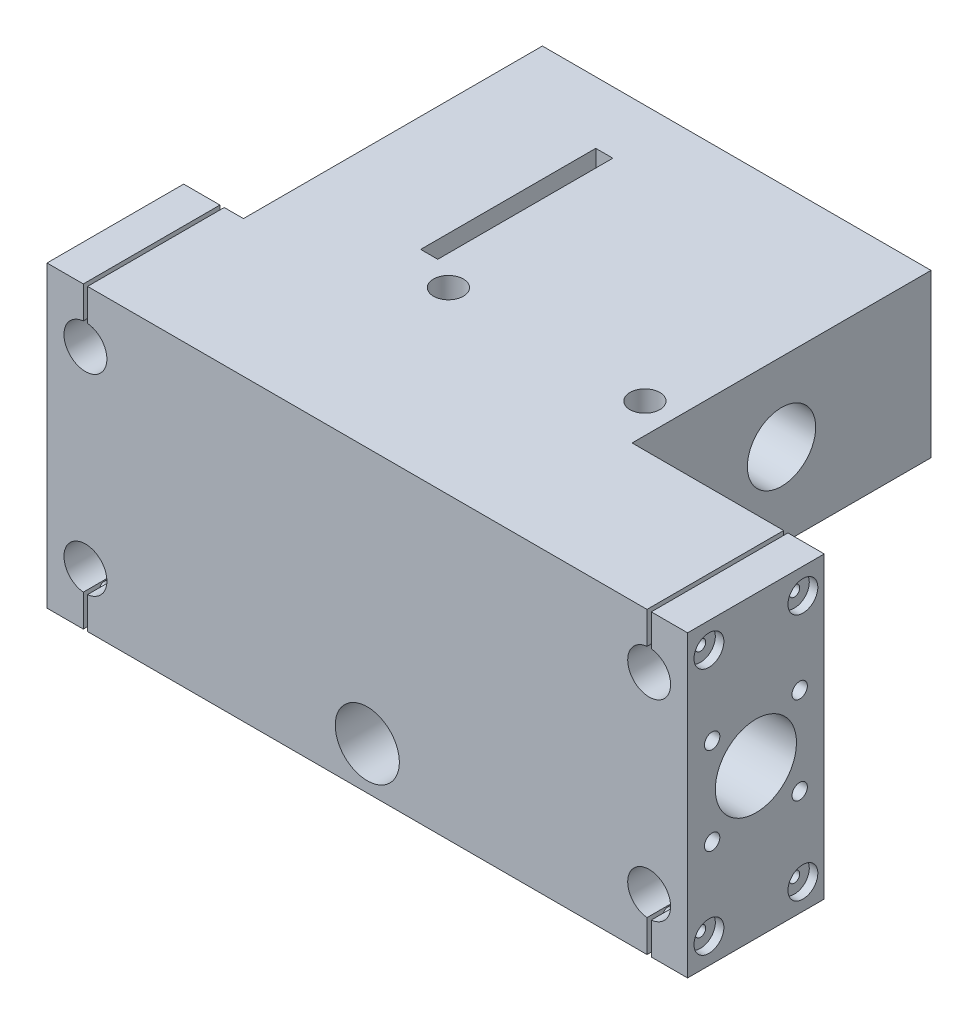
SolidWorks part; units mm, degrees
material "1060 Alloy"
ref_plane "Front Plane" through (0, 0, 0) normal (0, 0, 1) x (1, 0, 0)
ref_plane "Top Plane" through (0, 0, 0) normal (0, 1, 0) x (1, 0, 0)
ref_plane "Right Plane" through (0, 0, 0) normal (1, 0, 0) x (0, 0, -1)
sketch "Sketch1" plane through (0, 0, 0) normal (0, 0, 1) x (1, 0, 0)
  line L1 (-150, 0) -> (0, 0)
  line L2 (-150, 0) -> (-150, -70)
  line L3 (-150, -70) -> (0, -70)
  line L4 (0, 0) -> (0, -70)
  dimension "D1" = 150
  dimension "D2" = 70
extrude "Boss-Extrude1" add sketch "Sketch1" along normal blind 32
sketch "Sketch2" plane through (-150, 0, 0) normal (-1, 0, 0) x (0, 0, 1)
  line L0 (16, 0) -> (16, -70) construction
  line L1 (32, 0) -> (0, 0) construction
  line L2 (32, -70) -> (0, -70) construction
  line L3 (0, -35) -> (32, -35) construction
  line L4 (0, 0) -> (0, -70) construction
  line L5 (32, 0) -> (32, -70) construction
  circle A0 centre (16, -35) radius 9.5
  dimension "D1" = 19
extrude "Linear_bearing-cut-1" cut sketch "Sketch2" against normal blind 55
sketch "Sketch5" plane through (0, 0, 32) normal (0, 0, 1) x (1, 0, 0)
  line L0 (-75, 0) -> (-75, -70) construction
  line L1 (0, 0) -> (-150, 0) construction
  line L2 (-150, -70) -> (0, -70) construction
  line L3 (0, -35) -> (-150, -35) construction
  line L4 (0, -70) -> (0, 0) construction
  line L5 (-150, 0) -> (-150, -70) construction
  line L6 (-141, 0) -> (-141, -12.5) construction
  line L7 (-141, -12.5) -> (-9, -12.5) construction
  line L8 (-9, -12.5) -> (-9, 0) construction
  line L9 (-9, -57.5) -> (-9, -70) construction
  line L10 (-141, -57.5) -> (-9, -57.5) construction
  line L11 (-141, -70) -> (-141, -57.5) construction
  line L12 (-141.5, 0) -> (-141.5, -7.5)
  line L13 (-140.5, 0) -> (-140.5, -7.5)
  line L14 (-8.5, 0) -> (-8.5, -7.5)
  line L15 (-9.5, 0) -> (-9.5, -7.5)
  line L16 (-141.5, -70) -> (-141.5, -62.5)
  line L17 (-140.5, -70) -> (-140.5, -62.5)
  line L18 (-9.5, -70) -> (-9.5, -62.5)
  line L19 (-8.5, -70) -> (-8.5, -62.5)
  line L20 (-141.5, 0) -> (-140.5, 0)
  line L21 (-9.5, 0) -> (-8.5, 0)
  line L22 (-9.5, -70) -> (-8.5, -70)
  line L23 (-141.5, -70) -> (-140.5, -70)
  arc A0 (-141.5, -7.5) -> (-140.5, -7.5) centre (-141, -12.5) ccw
  arc A1 (-8.5, -7.5) -> (-9.5, -7.5) centre (-9, -12.5) cw
  arc A2 (-141.5, -62.5) -> (-140.5, -62.5) centre (-141, -57.5) cw
  arc A3 (-8.5, -62.5) -> (-9.5, -62.5) centre (-9, -57.5) ccw
  dimension "D1" = 9
  dimension "D3" = 12.5
  dimension "D5" = 0.5
  dimension "D6" = 7.5
extrude "Y-axis-shafts-cut" cut sketch "Sketch5" against normal through all
sketch "Sketch6" plane through (-95, 0, 0) normal (-1, 0, 0) x (0, 0, 1)
  line L0 (16, -25.5) -> (16, -44.5) construction
  circle A0 centre (16, -35) radius 9.5 construction
  circle A1 centre (16, -35) radius 9.5 construction
  circle A2 centre (16, -35) radius 6
  dimension "D1" = 12
sketch "Sketch7" plane through (0, 0, 0) normal (1, 0, 0) x (0, 0, -1)
  circle A0 centre (-16, -35) radius 9.5
  dimension "D1" = 19
extrude "Linear-bearing-cut-2" cut sketch "Sketch7" against normal blind 55
extrude "between-bearings" cut sketch "Sketch6" against normal through all
sketch "Sketch8" plane through (-150, 0, 0) normal (-1, 0, 0) x (0, 0, 1)
  line L0 (5, 0) -> (5, -6) construction
  line L1 (32, 0) -> (0, 0) construction
  line L2 (5, -6) -> (27, -6) construction
  line L3 (27, -6) -> (27, 0) construction
  line L4 (0, 0) -> (0, -70) construction
  line L5 (32, 0) -> (32, -70) construction
  line L6 (16, 0) -> (16, -70) construction
  line L7 (32, -70) -> (0, -70) construction
  line L8 (0, -35) -> (32, -35) construction
  line L9 (5, -39.9148) -> (4.7174, -39.9148) construction
  circle A0 centre (5, -6) radius 3.5
  circle A1 centre (27, -6) radius 3.5
  circle A2 centre (27, -64) radius 3.5
  circle A3 centre (5, -64) radius 3.5
  dimension "D4" = 7
  dimension "D1" = 5
  dimension "D3" = 6
extrude "shaft-holder-screw-cut" cut sketch "Sketch8" against normal blind 4
sketch "Sketch9" plane through (-146, 0, 0) normal (-1, 0, 0) x (0, 0, 1)
  line L0 (5, -2.5) -> (5, -9.5) construction
  line L1 (27, -2.5) -> (27, -9.5) construction
  line L2 (27, -60.5) -> (27, -67.5) construction
  line L3 (5, -60.5) -> (5, -67.5) construction
  circle A0 centre (5, -6) radius 3.5 construction
  circle A1 centre (5, -6) radius 3.5 construction
  circle A2 centre (27, -6) radius 3.5 construction
  circle A3 centre (27, -6) radius 3.5 construction
  circle A4 centre (27, -64) radius 3.5 construction
  circle A5 centre (27, -64) radius 3.5 construction
  circle A6 centre (5, -64) radius 3.5 construction
  circle A7 centre (5, -64) radius 3.5 construction
  circle A8 centre (5, -6) radius 1.25
  circle A9 centre (27, -6) radius 1.25
  circle A10 centre (5, -64) radius 1.25
  circle A11 centre (27, -64) radius 1.25
  dimension "D1" = 2.5
extrude "shaft-holder-screw-cut2" cut sketch "Sketch9" against normal blind 20
sketch "Sketch10" plane through (0, 0, 0) normal (1, 0, 0) x (0, 0, -1)
  line L0 (-27, 0) -> (-27, -6) construction
  line L1 (-32, 0) -> (0, 0) construction
  line L2 (-27, -6) -> (-5, -6) construction
  line L3 (-5, -6) -> (-5, 0) construction
  line L4 (-32, -70) -> (-32, 0) construction
  line L5 (0, -70) -> (0, 0) construction
  line L6 (-16, 0) -> (-16, -70) construction
  line L7 (-32, -70) -> (0, -70) construction
  line L8 (-32, -35) -> (0, -35) construction
  circle A0 centre (-27, -6) radius 3.5
  circle A1 centre (-5, -6) radius 3.5
  circle A2 centre (-5, -64) radius 3.5
  circle A3 centre (-27, -64) radius 3.5
  dimension "D4" = 7
  dimension "D1" = 5
  dimension "D2" = 6
extrude "shaft-holder-screw-cut-3" cut sketch "Sketch10" against normal blind 2
sketch "Sketch11" plane through (-2, 0, 0) normal (1, 0, 0) x (0, 0, -1)
  line L0 (-27, -2.5) -> (-27, -9.5) construction
  line L1 (-5, -2.5) -> (-5, -9.5) construction
  line L2 (-5, -60.5) -> (-5, -67.5) construction
  line L3 (-27, -60.5) -> (-27, -67.5) construction
  circle A0 centre (-27, -6) radius 3.5 construction
  circle A1 centre (-27, -6) radius 3.5 construction
  circle A2 centre (-5, -6) radius 3.5 construction
  circle A3 centre (-5, -6) radius 3.5 construction
  circle A4 centre (-5, -64) radius 3.5 construction
  circle A5 centre (-5, -64) radius 3.5 construction
  circle A6 centre (-27, -64) radius 3.5 construction
  circle A7 centre (-27, -64) radius 3.5 construction
  circle A8 centre (-27, -6) radius 1.25
  circle A9 centre (-5, -6) radius 1.25
  circle A10 centre (-5, -64) radius 1.25
  circle A11 centre (-27, -64) radius 1.25
  dimension "D1" = 2.5
extrude "shaft-holder-screw-cut-4" cut sketch "Sketch11" against normal blind 20
sketch "Sketch12" plane through (0, 0, 0) normal (1, 0, 0) x (0, 0, -1)
  line L0 (-5.75, 0) -> (-5.75, -24.75) construction
  line L1 (-32, 0) -> (0, 0) construction
  line L2 (-5.75, -24.75) -> (0, -24.75) construction
  line L3 (0, -70) -> (0, 0) construction
  line L4 (-16, 0) -> (-16, -70) construction
  line L5 (-32, -70) -> (0, -70) construction
  line L6 (0, -35) -> (-32, -35) construction
  line L7 (-32, -70) -> (-32, 0) construction
  circle A0 centre (-5.75, -24.75) radius 1.8
  circle A1 centre (-26.25, -24.75) radius 1.8
  circle A2 centre (-5.75, -45.25) radius 1.8
  circle A3 centre (-26.25, -45.25) radius 1.8
  dimension "D3" = 3.6
  dimension "D1" = 5.75
  dimension "D2" = 24.75
extrude "Linear-bearing-srew1" cut sketch "Sketch12" against normal blind 14
sketch "Sketch13" plane through (-150, 0, 0) normal (-1, 0, 0) x (0, 0, 1)
  line L0 (27.5, 0) -> (27.5, -24.75) construction
  line L1 (32, 0) -> (0, 0) construction
  line L2 (27.5, -24.75) -> (32, -24.75) construction
  line L3 (32, 0) -> (32, -70) construction
  line L4 (16, 0) -> (16, -70) construction
  line L5 (32, -70) -> (0, -70) construction
  line L6 (32, -35) -> (0, -35) construction
  line L7 (0, 0) -> (0, -70) construction
  circle A0 centre (27.5, -24.75) radius 1.85
  circle A1 centre (4.5, -24.75) radius 1.85
  circle A2 centre (27.5, -45.25) radius 1.85
  circle A3 centre (4.5, -45.25) radius 1.85
  dimension "D3" = 3.7
  dimension "D1" = 24.75
  dimension "D2" = 4.5
extrude "Linear-bearing-screw2" cut sketch "Sketch13" against normal blind 14
sketch "Sketch14" plane through (0, 0, 0) normal (0, 0, -1) x (-1, 0, 0)
  line L0 (140.5, -70) -> (9.5, -70) construction
  line L1 (0, -70) -> (0, 0) construction
  circle A0 centre (75, -60) radius 7.5
  dimension "D3" = 15
  dimension "D1" = 10
  dimension "D2" = 75
extrude "Cut-Extrude1" cut sketch "Sketch14" against normal through all
sketch "Sketch15" plane through (0, 0, 0) normal (0, 0, -1) x (-1, 0, 0)
  line L0 (9.5, 0) -> (140.5, 0) construction
  line L1 (45, 0) -> (105, 0)
  line L2 (45, 0) -> (45, -38)
  line L3 (45, -38) -> (105, -38)
  line L4 (105, 0) -> (105, -38)
  line L5 (75, -70) -> (75, 0) construction
  line L6 (140.5, -70) -> (9.5, -70) construction
  point P10 (75, 0)
  dimension "D1" = 38
  dimension "D2" = 60
extrude "Boss-Extrude2" add sketch "Sketch15" along normal blind 70
sketch "Sketch17" plane through (0, -38, 0) normal (0, -1, 0) x (1, 0, 0)
  line L0 (-45, -70) -> (-105, -70) construction
  line L1 (-105, -70) -> (-105, 0) construction
  line L2 (-45, -70) -> (-45, 0) construction
  circle A0 centre (-98, -10) radius 3.5
  circle A1 centre (-52, -10) radius 3.5
  dimension "D4" = 7
  dimension "D1" = 60
  dimension "D2" = 7
  dimension "D3" = 7
extrude "Cut-Extrude3" cut sketch "Sketch17" against normal up to next
sketch "Sketch18" plane through (-105, 0, 0) normal (-1, 0, 0) x (0, 0, 1)
  line L1 (-70, 0) -> (0, 0)
  line L2 (-70, 0) -> (-70, -38)
  line L3 (-70, -38) -> (0, -38)
  line L4 (0, 0) -> (0, -38)
extrude "Boss-Extrude3" add sketch "Sketch18" along normal blind 31
sketch "Sketch19" plane through (-45, 0, 0) normal (1, 0, 0) x (0, 0, -1)
  line L0 (70, 0) -> (70, -38) construction
  line L1 (70, 0) -> (0, 0) construction
  circle A0 centre (35, -18.3) radius 8
  dimension "D1" = 16
  dimension "D2" = 35
  dimension "D3" = 18.3
extrude "Cut-Extrude4" cut sketch "Sketch19" against normal through all
sketch "Sketch20" plane through (-136, 0, 0) normal (-1, 0, 0) x (0, 0, 1)
  line L0 (-35, -10.3) -> (-35, -26.3) construction
  circle A0 centre (-35, -18.3) radius 8 construction
  circle A1 centre (-35, -18.3) radius 11
  circle A2 centre (-23.6863, -6.9863) radius 2.5
  circle A3 centre (-19, -18.3) radius 2.5
  circle A4 centre (-23.6863, -29.6137) radius 2.5
  circle A5 centre (-46.3137, -6.9863) radius 2.5
  circle A6 centre (-51, -18.3) radius 2.5
  circle A7 centre (-46.3137, -29.6137) radius 2.5
  point P19 (0, 0)
  point P20 (0, 0)
  point P21 (0, 0)
  point P22 (0, 0)
  point P23 (0, 0)
  point P24 (0, 0)
  point P25 (0, 0)
  point P26 (0, 0)
  point P27 (0, 0)
  point P28 (0, 0)
  point P30 (-42.394, 6.9942)
  dimension "D1" = 22
  dimension "D8" = 5
  dimension "D2" = 16
  dimension "D3" = 16
  dimension "D4" = 16
  dimension "D5" = 16
  dimension "D6" = 16
  dimension "D7" = 45
extrude "Cut-Extrude5" cut sketch "Sketch20" against normal blind 31
sketch "Sketch21" plane through (0, -38, 0) normal (0, -1, 0) x (-1, 0, 0)
  line L0 (45, 70) -> (136, 70) construction
  line L1 (109, 14.5) -> (105, 14.5)
  line L2 (109, 14.5) -> (109, 55.5)
  line L3 (109, 55.5) -> (105, 55.5)
  line L4 (105, 14.5) -> (105, 55.5)
  line L5 (136, 70) -> (136, 0) construction
  point P8 (107, 14.5)
  dimension "D1" = 14.5
  dimension "D2" = 27
  dimension "D3" = 31
  dimension "D4" = 55.5
extrude "Cut-Extrude6" cut sketch "Sketch21" against normal up to next
